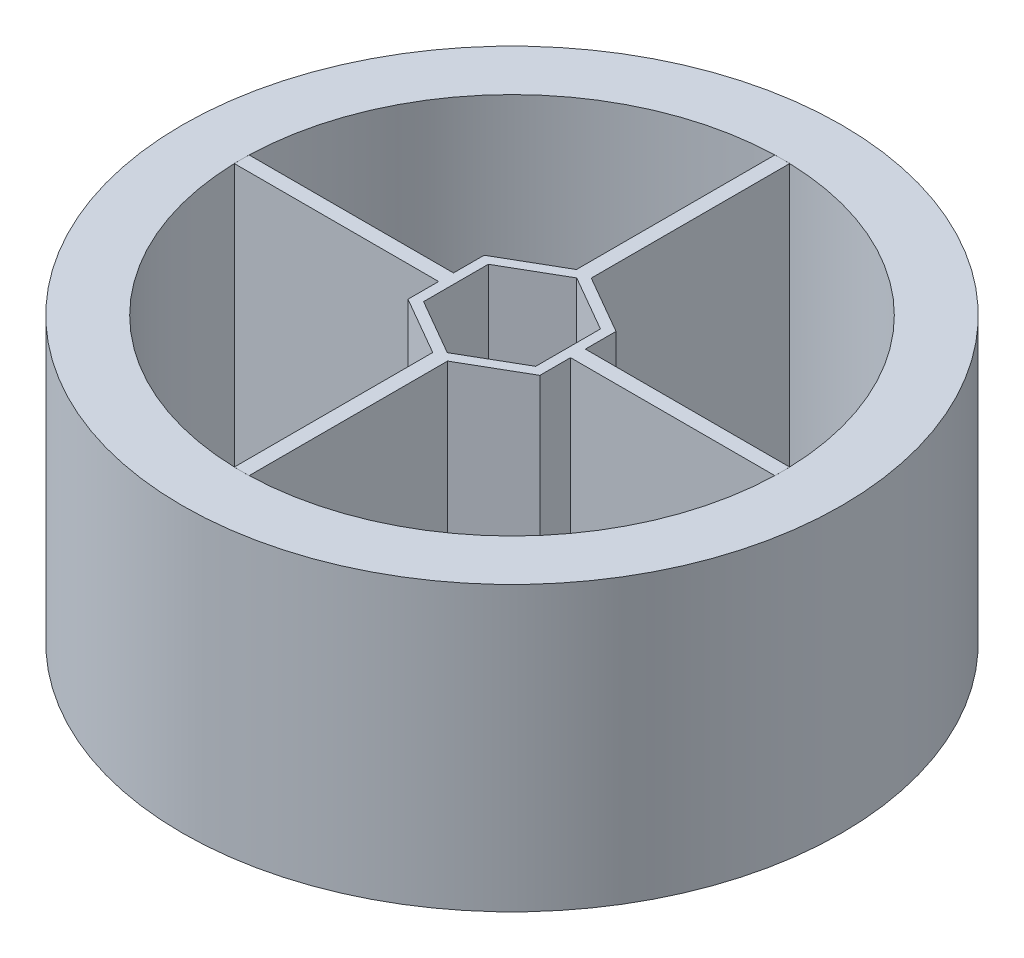
SolidWorks part; units mm, degrees
ref_plane "Front Plane" through (0, 0, 0) normal (0, 0, 1) x (1, 0, 0)
ref_plane "Top Plane" through (0, 0, 0) normal (0, 1, 0) x (1, 0, 0)
ref_plane "Right Plane" through (0, 0, 0) normal (1, 0, 0) x (0, 0, -1)
sketch "Sketch1" plane through (0, 0, 0) normal (0, 1, 0) x (1, 0, 0)
  line L0 (-1.125, -41) -> (-1.125, 41)
  line L1 (-1.125, -41) -> (1.125, -41)
  line L2 (-1.125, 41) -> (1.125, 41)
  line L3 (1.125, -41) -> (1.125, 41)
  line L4 (-1.125, -41) -> (1.125, 41) construction
  line L5 (-1.125, 41) -> (1.125, -41) construction
  line L6 (-41, 1.125) -> (41, 1.125)
  line L7 (-41, 1.125) -> (-41, -1.125)
  line L8 (41, 1.125) -> (41, -1.125)
  line L9 (-41, -1.125) -> (41, -1.125)
  line L10 (-41, 1.125) -> (41, -1.125) construction
  line L11 (41, 1.125) -> (-41, -1.125) construction
  line L13 (0, 11.547) -> (-10, 5.7735)
  line L14 (-10, 5.7735) -> (-10, -5.7735)
  line L15 (-10, -5.7735) -> (0, -11.547)
  line L16 (0, -11.547) -> (10, -5.7735)
  line L17 (10, -5.7735) -> (10, 5.7735)
  line L18 (10, 5.7735) -> (0, 11.547)
  circle A0 centre (0, 0) radius 50
  circle A1 centre (0, 0) radius 41
  circle A2 centre (0, 0) radius 10 construction
  dimension "D1" = 100
  dimension "D2" = 82
  dimension "D3" = 2.25
  dimension "D4" = 2.25
  dimension "D5" = 20
  dimension "D6" = 82
  dimension "D7" = 82
extrude "main-wheel" add sketch "Sketch1" along normal blind 43 contours A0 A1 L3 L1 L0 L9 L7 L6 L2 L8 | L6 A1 L9 L14 | L9 A1 L6 L17 | L3 A1 L0 L13 L18 | A1 L3 L16 L15 L0 | L14 L15 L0 L9 | L6 L14 L9 L0 | L9 L17 L6 L3 | L16 L17 L9 L3 | L15 L16 L3 L9 L0 | L0 L9 L3 L6 | L3 L18 L13 L0 L6 | L17 L18 L3 L6 | L13 L14 L6 L0 region at (0, 0, 26.108) region at (-5.0369, 0, 4.882) region at (0, 0, 6.1754) region at (-25.4974, 0, 0) region at (-5.5625, 0, 0) region at (0, 0, 0) region at (5.0369, 0, 4.882) region at (25.4974, 0, 0) region at (-5.0369, 0, -4.882) region at (0, 0, -6.1754) region at (5.5625, 0, 0) region at (0, 0, -26.108) region at (5.0369, 0, -4.882) region at (-48.5858, 0, 0)
sketch "Sketch2" plane through (0, 43, 0) normal (0, 1, 0) x (1, 0, 0)
  line L1 (0, -9.815) -> (8.5, -4.9075)
  line L2 (8.5, -4.9075) -> (8.5, 4.9075)
  line L3 (8.5, 4.9075) -> (0, 9.815)
  line L4 (0, 9.815) -> (-8.5, 4.9075)
  line L5 (-8.5, 4.9075) -> (-8.5, -4.9075)
  line L6 (-8.5, -4.9075) -> (0, -9.815)
  circle A0 centre (0, 0) radius 8.5 construction
  dimension "D1" = 17
extrude "hex-bore" cut sketch "Sketch2" against normal blind 23
sketch "Sketch3" plane through (0, 20, 0) normal (0, 1, 0) x (1, 0, 0)
  circle A0 centre (0, 0) radius 2.5
  dimension "D1" = 5
extrude "motor-bore" cut sketch "Sketch3" against normal through all
